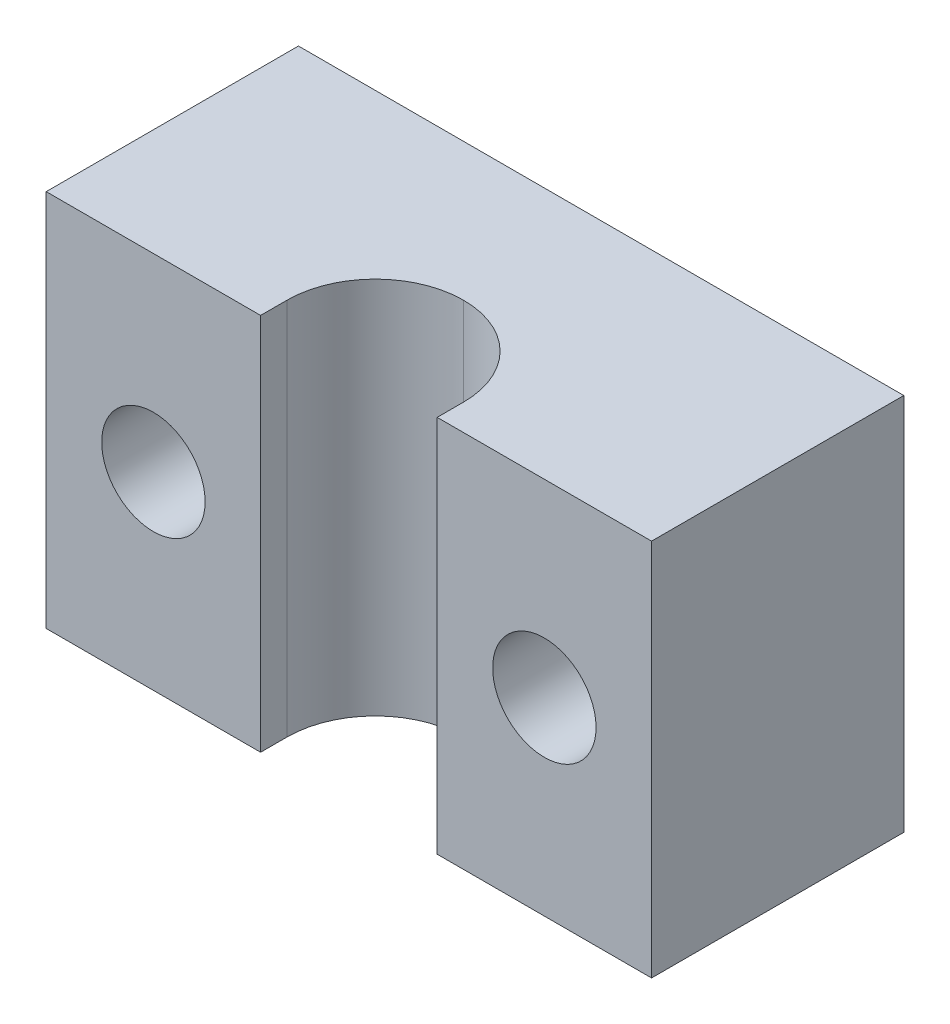
SolidWorks part; units mm, degrees
ref_plane "Спереди" through (0, 0, 0) normal (0, 0, 1) x (1, 0, 0)
ref_plane "Сверху" through (0, 0, 0) normal (0, 1, 0) x (1, 0, 0)
ref_plane "Справа" through (0, 0, 0) normal (1, 0, 0) x (0, 0, -1)
sketch "Sketch1" plane through (0, 0, 0) normal (0, 1, 0) x (1, 0, 0)
  line L0 (-22.986, 8.6014) -> (-22.986, -11.3986)
  line L1 (-22.986, -11.3986) -> (-5.986, -11.3986)
  line L2 (-5.986, -11.3986) -> (-5.986, -2.3077)
  line L3 (-5.986, -2.3077) -> (8.014, -2.3077)
  line L4 (8.014, -2.3077) -> (8.014, -11.3986)
  line L5 (8.014, -11.3986) -> (25.014, -11.3986)
  line L6 (25.014, -11.3986) -> (25.014, 8.6014)
  line L7 (25.014, 8.6014) -> (6.014, 8.6014)
  line L8 (6.014, 8.6014) -> (6.014, 58.6014)
  line L9 (6.014, 58.6014) -> (-3.986, 58.6014)
  line L10 (-3.986, 58.6014) -> (-3.986, 8.6014)
  line L11 (-3.986, 8.6014) -> (-22.986, 8.6014)
  dimension "D1" = 20
  dimension "D2" = 48
  dimension "D3" = 50
  dimension "D4" = 10
  dimension "D5" = 14
extrude "Boss-Extrude1" add sketch "Sketch1" along normal blind 30
sketch "Sketch3" plane through (0, 0, 11.3986) normal (0, 0, 1) x (1, 0, 0)
  line L0 (-22.986, 15) -> (-5.986, 15) construction
  line L1 (-22.986, 30) -> (-22.986, 0) construction
  line L2 (-5.986, 30) -> (-5.986, 0) construction
  line L4 (8.014, 15) -> (25.014, 15) construction
  line L5 (8.014, 30) -> (8.014, 0) construction
  line L6 (25.014, 30) -> (25.014, 0) construction
  circle A0 centre (-14.486, 15) radius 4.1
  circle A1 centre (16.514, 15) radius 4.1
  dimension "D1" = 8.2
extrude "Cut-Extrude1" cut sketch "Sketch3" against normal through all
sketch "Sketch4" plane through (6.014, 0, 0) normal (1, 0, 0) x (0, 0, -1)
  line L0 (58.6014, 15) -> (8.6014, 15) construction
  line L1 (58.6014, 30) -> (58.6014, 0) construction
  line L2 (8.6014, 30) -> (8.6014, 0) construction
  circle A0 centre (28.6014, 15) radius 4.1
  circle A1 centre (48.6014, 15) radius 4.1
  dimension "D1" = 8.2
  dimension "D2" = 20
  dimension "D3" = 20
extrude "Cut-Extrude2" cut sketch "Sketch4" against normal through all
fillet "Fillet1" radius 7 2 edges at (-5.986, 15, 2.3077) (8.014, 15, 2.3077)
sketch "Sketch6" plane through (0, 30, 0) normal (0, 1, 0) x (1, 0, 0)
  line L0 (-3.986, 8.6014) -> (6.014, 8.6014)
  line L1 (6.014, 8.6014) -> (6.014, 58.6014)
  line L2 (6.014, 58.6014) -> (-3.986, 58.6014)
  line L3 (-3.986, 58.6014) -> (-3.986, 8.6014)
extrude "Cut-Extrude3" cut sketch "Sketch6" against normal through all
